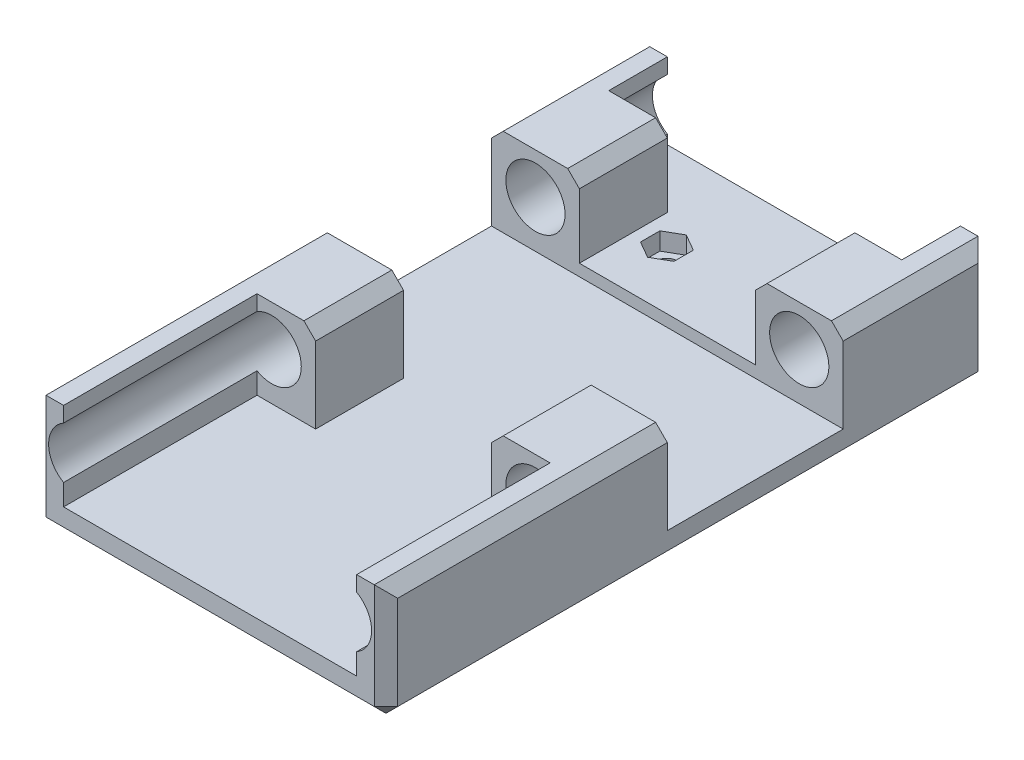
SolidWorks part; units mm, degrees
ref_plane "Front Plane" through (0, 0, 0) normal (0, 0, 1) x (1, 0, 0)
ref_plane "Top Plane" through (0, 0, 0) normal (0, 1, 0) x (1, 0, 0)
ref_plane "Right Plane" through (0, 0, 0) normal (1, 0, 0) x (0, 0, -1)
sketch "Sketch1" plane through (0, 0, 0) normal (0, 1, 0) x (1, 0, 0)
  line L1 (30, 30) -> (-30, 30)
  line L2 (30, 30) -> (30, -30)
  line L3 (30, -30) -> (-30, -30)
  line L4 (-30, 30) -> (-30, -30)
  line L5 (30, 30) -> (-30, -30) construction
  line L6 (30, -30) -> (-30, 30) construction
  point P0 (0, 0)
  dimension "D1" = 60
  dimension "D2" = 60
extrude "Boss-Extrude1" add sketch "Sketch1" along normal blind 5
sketch "Sketch2" plane through (0, 5, 0) normal (0, 1, 0) x (1, 0, 0)
  line L0 (-30, 30) -> (-30, -30) construction
  line L1 (-30, 30) -> (-15, 30)
  line L2 (-30, 30) -> (-30, 15)
  line L3 (-30, 15) -> (-15, 15)
  line L4 (-15, 30) -> (-15, 15)
  line L5 (30, -30) -> (30, 30) construction
  line L6 (30, 30) -> (15, 30)
  line L7 (30, 30) -> (30, 15)
  line L8 (30, 15) -> (15, 15)
  line L9 (15, 30) -> (15, 15)
  line L10 (30, 30) -> (-30, 30) construction
  line L11 (-30, -15) -> (-15, -15)
  line L12 (-30, -15) -> (-30, -30)
  line L13 (-30, -30) -> (-15, -30)
  line L14 (-15, -15) -> (-15, -30)
  line L15 (30, -15) -> (15, -15)
  line L16 (30, -15) -> (30, -30)
  line L17 (30, -30) -> (15, -30)
  line L18 (15, -15) -> (15, -30)
  line L19 (-30, -30) -> (30, -30) construction
  dimension "D1" = 15
  dimension "D2" = 15
extrude "Boss-Extrude2" add sketch "Sketch2" along normal blind 15
sketch "Sketch3" plane through (0, 0, 30) normal (0, 0, 1) x (1, 0, 0)
  line L0 (-30, 13) -> (30, 13) construction
  line L2 (30, 20) -> (30, 0) construction
  line L3 (-30, 20) -> (-30, 0) construction
  line L4 (-15, 5) -> (15, 5) construction
  line L5 (-22.5, 20) -> (-22.5, 0) construction
  line L6 (-30, 20) -> (-15, 20) construction
  line L7 (-30, 0) -> (30, 0) construction
  line L8 (22.5, 20) -> (22.5, 0) construction
  line L9 (15, 20) -> (30, 20) construction
  circle A0 centre (-22.5, 13) radius 5.05
  circle A1 centre (22.5, 13) radius 5.05
  point P3 (0, 13)
  point P19 (-22.5, 13)
  point P20 (22.5, 13)
  dimension "D2" = 10.1
  dimension "D3" = 10.1
  dimension "D1" = 8
extrude "Cut-Extrude1" cut sketch "Sketch3" against normal through all both and the other way through all
sketch "Sketch4" plane through (0, 0, 30) normal (0, 0, 1) x (1, 0, 0)
  line L0 (30, 20) -> (30, 0) construction
  line L1 (-30, 0) -> (30, 0)
  line L2 (-30, 0) -> (-30, 5)
  line L3 (-30, 5) -> (30, 5)
  line L4 (30, 0) -> (30, 5)
  line L5 (-15, 5) -> (15, 5) construction
extrude "Boss-Extrude3" add sketch "Sketch4" along normal blind 33
sketch "Sketch5" plane through (0, 0, -30) normal (0, 0, -1) x (-1, 0, 0)
  line L1 (-30, 0) -> (30, 0)
  line L2 (-30, 0) -> (-30, 5)
  line L3 (-30, 5) -> (30, 5)
  line L4 (30, 0) -> (30, 5)
extrude "Boss-Extrude4" add sketch "Sketch5" along normal blind 10
sketch "Sketch6" plane through (0, 5, 0) normal (0, 1, 0) x (1, 0, 0)
  line L0 (30, 40) -> (30, 30) construction
  line L5 (15, 30) -> (30, 30) construction
  line L6 (15, 30) -> (15, 15) construction
  line L8 (-15, 15) -> (-15, 30) construction
  line L9 (-30, 30) -> (-15, 30) construction
  line L10 (-30, 40) -> (-30, 30) construction
  line L11 (-30, 40) -> (30, 40) construction
  line L12 (30, 40) -> (30, 30)
  line L13 (15, 30) -> (30, 30)
  line L14 (15, 30) -> (15, 15)
  line L15 (-15, 15) -> (-15, 30)
  line L16 (-30, 30) -> (-15, 30)
  line L17 (-30, 40) -> (-30, 30)
  line L18 (-30, 40) -> (30, 40)
  line L19 (-15, 15) -> (15, 15)
extrude "Boss-Extrude5" add sketch "Sketch6" along normal blind 2
sketch "Sketch8" plane through (0, 7, 0) normal (0, 1, 0) x (1, 0, 0)
  line L0 (0, 40) -> (0, -63) construction
  line L1 (30, 40) -> (-30, 40) construction
  line L2 (30, -63) -> (-30, -63) construction
  line L3 (-10.07, 25) -> (10.07, 25) construction
  line L5 (-7.2121, 23.35) -> (-7.2121, 26.65)
  line L6 (-7.2121, 26.65) -> (-10.07, 28.3)
  line L7 (-10.07, 28.3) -> (-12.9279, 26.65)
  line L8 (-12.9279, 26.65) -> (-12.9279, 23.35)
  line L9 (-12.9279, 23.35) -> (-10.07, 21.7)
  line L10 (-10.07, 21.7) -> (-7.2121, 23.35)
  line L11 (12.9279, 23.35) -> (12.9279, 26.65)
  line L12 (12.9279, 26.65) -> (10.07, 28.3)
  line L13 (10.07, 28.3) -> (7.2121, 26.65)
  line L14 (7.2121, 26.65) -> (7.2121, 23.35)
  line L15 (7.2121, 23.35) -> (10.07, 21.7)
  line L16 (10.07, 21.7) -> (12.9279, 23.35)
  circle A0 centre (-10.07, 25) radius 2.8579 construction
  circle A1 centre (10.07, 25) radius 2.8579 construction
  point P9 (0, 25)
  point P24 (10.07, 25)
  point P25 (-10.07, 25)
  dimension "D1" = 20.14
  dimension "D2" = 15
  dimension "D3" = 3.3
extrude "Cut-Extrude2" cut sketch "Sketch8" against normal blind 3
hole_wizard "M3 Clearance Hole1" positions "Sketch10" profile "Sketch11" hole size "M3" standard "ANSI Metric" end condition through all
sketch "Sketch10" plane through (0, 7, 0) normal (0, 1, 0) x (1, 0, 0)
  point P0 (-10.07, 25)
  point P3 (10.07, 25)
sketch "Sketch11" plane through (-10.07, 7, -25) normal (1, 0, 0) x (0, 0, 1)
  line L0 (0, 0) -> (0, 7)
  line L1 (0, 7) -> (1.7, 7)
  line L2 (1.7, 7) -> (1.7, 0.025)
  line L3 (1.7, 0.025) -> (1.725, 0)
  line L5 (1.725, 0) -> (0, 0)
  line L6 (-1.7, 0.025) -> (-1.725, 0) construction
  line L11 (0, -6.35) -> (0, 107.95) construction
  dimension "Thru Hole Dia." = 3.4
  dimension "Thru Hole Depth" = 7
  dimension "Near C'Sink Dia." = 3.45
  dimension "Near C'Sink Angle" = 90
sketch "Sketch13" plane through (0, 5, 0) normal (0, 1, 0) x (1, 0, 0)
  line L10 (30, -63) -> (-30, -63) construction
  line L11 (30, -30) -> (25, -30)
  line L12 (30, -30) -> (30, -63)
  line L13 (30, -63) -> (25, -63)
  line L14 (25, -30) -> (25, -63)
  line L15 (-15, 30) -> (-30, 30) construction
  line L16 (-30, -30) -> (-25, -30)
  line L17 (-30, -30) -> (-30, -63)
  line L18 (-30, -63) -> (-25, -63)
  line L19 (-25, -30) -> (-25, -63)
  line L20 (-30, 40) -> (-25, 40)
  line L21 (-30, 40) -> (-30, 30)
  line L22 (-30, 30) -> (-25, 30)
  line L23 (-25, 40) -> (-25, 30)
  line L24 (30, 30) -> (15, 30) construction
  line L25 (30, 40) -> (25, 40)
  line L26 (30, 40) -> (30, 30)
  line L27 (30, 30) -> (25, 30)
  line L28 (25, 40) -> (25, 30)
  dimension "D1" = 5
extrude "Boss-Extrude6" add sketch "Sketch13" along normal up to surface (15 mm away) up to face at (-22.5, 20, -22.5)
chamfer "Chamfer1" distance 2 angle 45 16 edges at (0, 0, -40) (30, 10, 63) (30, 10, -40) (30, 0, 11.5) (0, 0, 63) (-30, 10, 63) (-30, 0, 11.5) (-30, 10, -40) (30, 20, 39) (15, 20, 22.5) (-30, 20, 39) (-15, 20, 22.5) (30, 20, -27.5) (15, 20, -22.5) (-15, 20, -22.5) (-30, 20, -27.5)
sketch "Sketch14" plane through (0, 0, 30) normal (0, 0, 1) x (1, 0, 0)
  circle A0 centre (-22.5, 13) radius 5.05
  circle A1 centre (22.5, 13) radius 5.05
  arc A2 (-25, 8.6122) -> (-25, 17.3878) centre (-22.5, 13) ccw construction
extrude "Cut-Extrude3" cut sketch "Sketch14" against normal mid plane 200
